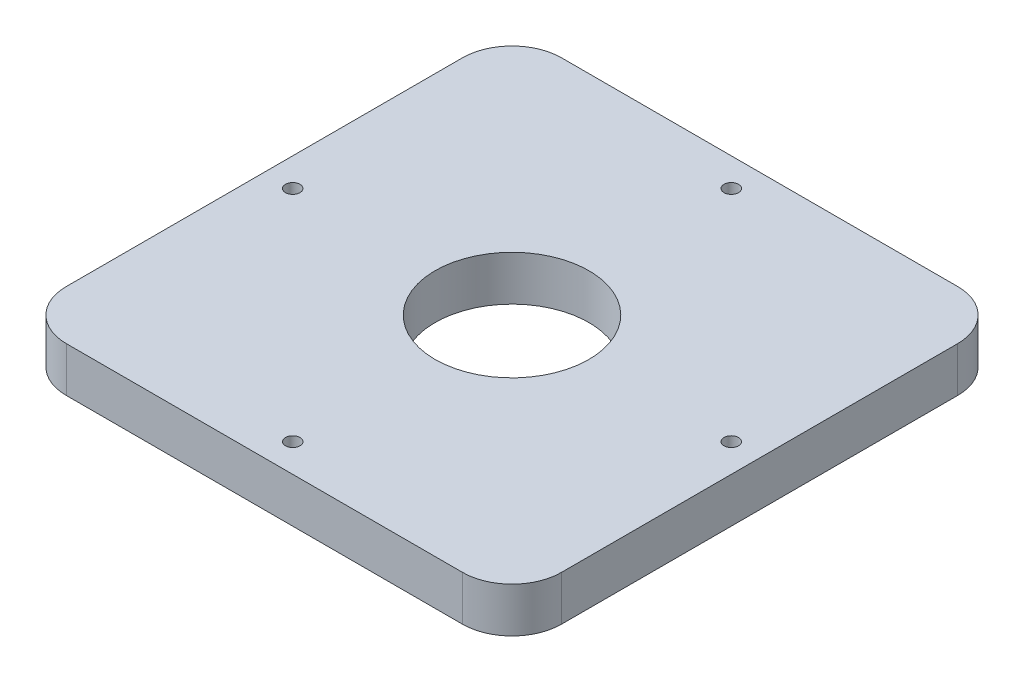
SolidWorks part; units mm, degrees
ref_plane "Front Plane" through (0, 0, 0) normal (0, 0, 1) x (1, 0, 0)
ref_plane "Top Plane" through (0, 0, 0) normal (0, 1, 0) x (1, 0, 0)
ref_plane "Right Plane" through (0, 0, 0) normal (1, 0, 0) x (0, 0, -1)
sketch "Sketch1" plane through (0, 0, 0) normal (0, 1, 0) x (1, 0, 0)
  line L1 (7, 0) -> (63, 0)
  line L2 (0, 7) -> (0, 63)
  line L3 (7, 70) -> (63, 70)
  line L4 (70, 7) -> (70, 63)
  arc A0 (63, 0) -> (70, 7) centre (63, 7) ccw
  arc A1 (7, 0) -> (0, 7) centre (7, 7) cw
  arc A2 (0, 63) -> (7, 70) centre (7, 63) cw
  arc A3 (63, 70) -> (70, 63) centre (63, 63) cw
  point P7 (70, 0)
  point P10 (0, 0)
  point P15 (70, 70)
  dimension "D3" = 7
  dimension "D1" = 70
  dimension "D2" = 70
extrude "Boss-Extrude1" add sketch "Sketch1" along normal blind 6.35
sketch "Sketch2" plane through (0, 6.35, 0) normal (0, 1, 0) x (1, 0, 0)
  line L0 (35, 70) -> (35, 0) construction
  line L1 (63, 70) -> (7, 70) construction
  line L2 (7, 0) -> (63, 0) construction
  line L3 (0, 35) -> (70, 35) construction
  line L4 (0, 63) -> (0, 7) construction
  line L5 (70, 7) -> (70, 63) construction
  circle A0 centre (35, 35) radius 10.875
  circle A1 centre (35, 66) radius 1.025
  circle A2 centre (35, 4) radius 1.025
  circle A3 centre (4, 35) radius 1.025
  circle A4 centre (66, 35) radius 1.025
  point P22 (0, 0)
  point P23 (0, 0)
  point P24 (0, 0)
  point P25 (0, 0)
  point P26 (0, 0)
  dimension "D1" = 21.75
  dimension "D2" = 2.05
  dimension "D3" = 2.05
  dimension "D4" = 2.05
  dimension "D5" = 2.05
  dimension "D6" = 4
  dimension "D7" = 4
  dimension "D8" = 4
  dimension "D9" = 4
extrude "Cut-Extrude1" cut sketch "Sketch2" against normal blind 6.35
